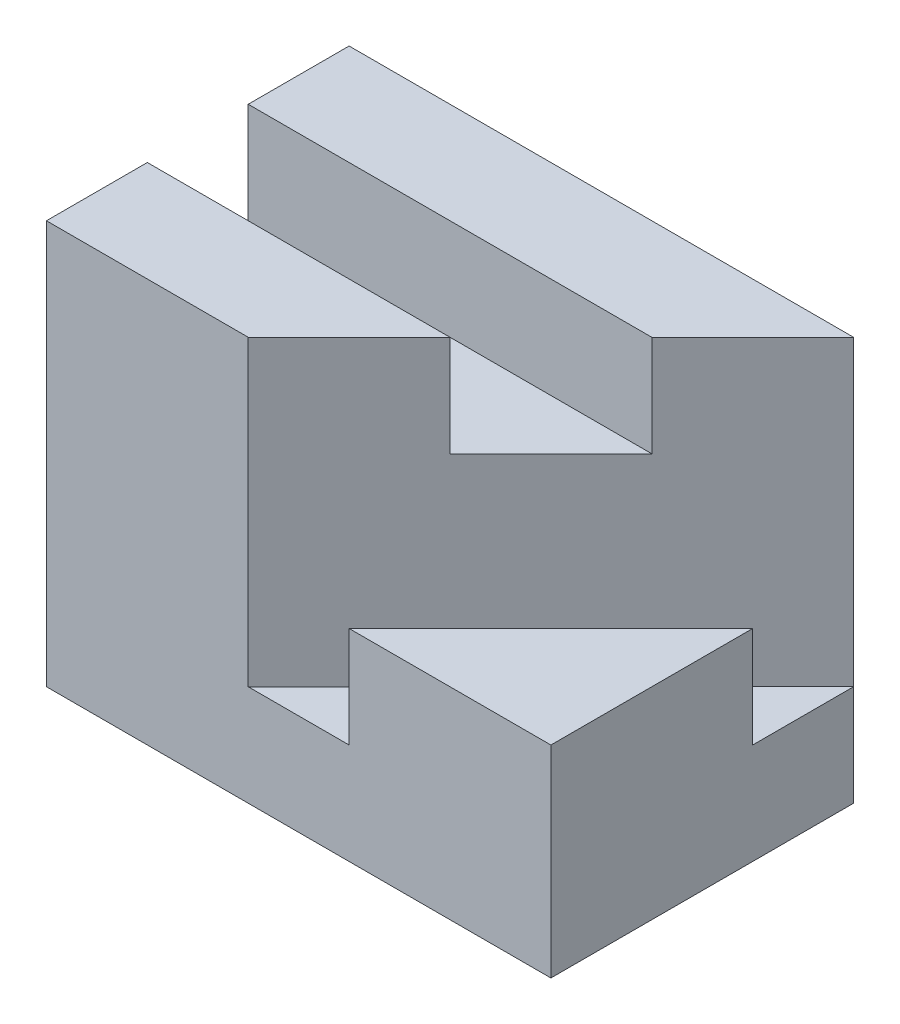
SolidWorks part; units mm, degrees
ref_plane "前基準面" through (0, 0, 0) normal (0, 0, 1) x (1, 0, 0)
ref_plane "上基準面" through (0, 0, 0) normal (0, 1, 0) x (1, 0, 0)
ref_plane "右基準面" through (0, 0, 0) normal (1, 0, 0) x (0, 0, -1)
sketch "草圖1" plane through (0, 0, 0) normal (0, 1, 0) x (1, 0, 0)
  line L1 (12.5, 7.5) -> (-12.5, 7.5)
  line L2 (12.5, 7.5) -> (12.5, -7.5)
  line L3 (12.5, -7.5) -> (-12.5, -7.5)
  line L4 (-12.5, 7.5) -> (-12.5, -7.5)
  line L5 (12.5, 7.5) -> (-12.5, -7.5) construction
  line L6 (12.5, -7.5) -> (-12.5, 7.5) construction
  point P0 (0, 0)
  dimension "D1" = 15
  dimension "D2" = 25
extrude "填料-伸長1" add sketch "草圖1" along normal blind 20
sketch "草圖3" plane through (0, 20, 0) normal (0, 1, 0) x (1, 0, 0)
  line L0 (-12.5, 7.5) -> (-12.5, -7.5) construction
  line L1 (-12.5, -2.5) -> (2.5, -2.5)
  line L2 (-12.5, -2.5) -> (-12.5, 2.5)
  line L3 (-12.5, 2.5) -> (7.5, 2.5)
  line L5 (12.5, 7.5) -> (7.5, 2.5)
  line L6 (-12.5, -7.5) -> (12.5, -7.5) construction
  line L7 (2.5, -7.5) -> (12.5, 2.5)
  line L8 (12.5, -7.5) -> (12.5, 7.5) construction
  line L9 (12.5, 7.5) -> (-12.5, 7.5) construction
  line L10 (2.5, -2.5) -> (-2.5, -7.5)
  line L11 (-2.5, -7.5) -> (2.5, -7.5)
  line L12 (12.5, 2.5) -> (12.5, 7.5)
  line L13 (7.5, 2.5) -> (2.5, -2.5)
  line L15 (-12.5, -7.5) -> (12.5, -7.5)
  line L16 (-12.5, -7.5) -> (-12.5, 7.5)
  line L17 (-12.5, 7.5) -> (12.5, 7.5)
  line L18 (12.5, -7.5) -> (12.5, 7.5)
  line M13 (-12.5, 7.5) -> (-12.5, -7.5)
  line M14 (-12.5, -7.5) -> (12.5, -7.5)
  line M15 (12.5, -7.5) -> (12.5, 7.5)
  dimension "D1" = 5
  dimension "D2" = 5
  dimension "D3" = 15
  dimension "D5" = 10
  dimension "D6" = 5
extrude "除料-伸長1" cut sketch "草圖3" against normal blind 5 contours L13 L3 L1 M13 | L5 L13 L10 L7 M14 M15 | L7 M14 M15 region at (-3.6905, 20, -0.119) region at (6.1667, 20, 1.1667) region at (9.1667, 20, 4.1667)
extrude "除料-伸長2" cut sketch "草圖3<3>" against normal blind 15 contours L5 L13 L10 L7 M14 M15 region at (6.1667, 20, 1.1667)
sketch "草圖3<3>" plane through (0, 20, 0) normal (0, 1, 0) x (1, 0, 0) same geometry as "草圖3"
extrude "除料-伸長3" cut sketch "草圖3<4>" against normal blind 10 contours L7 M14 M15 region at (9.1667, 20, 4.1667)
sketch "草圖3<4>" plane through (0, 20, 0) normal (0, 1, 0) x (1, 0, 0) same geometry as "草圖3"
